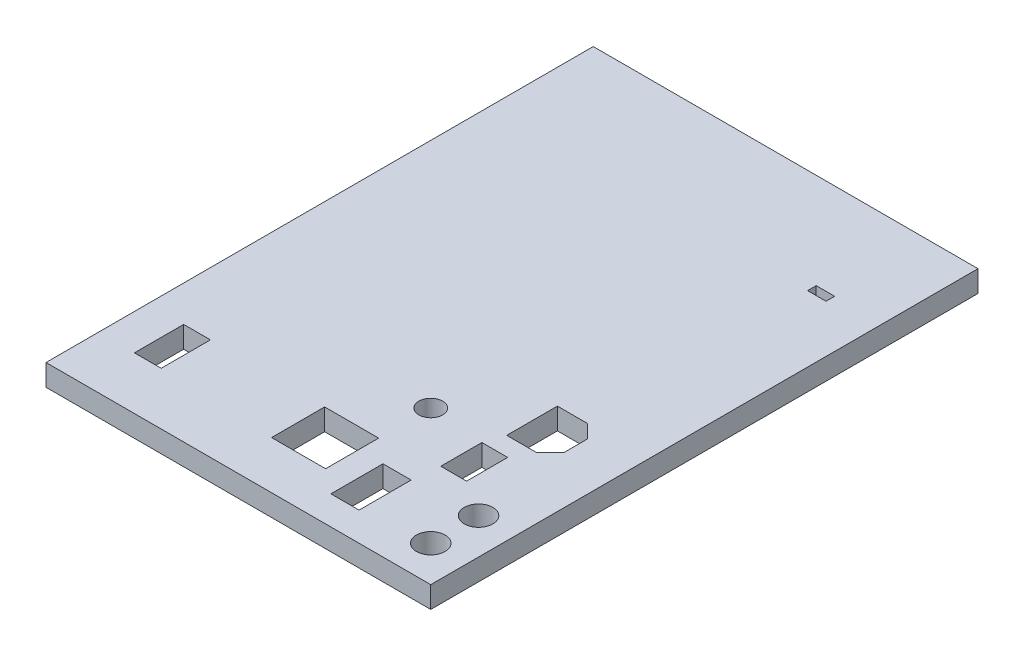
SolidWorks part; units mm, degrees
material "Perspex (TM) GS Acrylic Cast Sheet"
ref_plane "Front Plane" through (0, 0, 0) normal (0, 0, 1) x (1, 0, 0)
ref_plane "Top Plane" through (0, 0, 0) normal (0, 1, 0) x (1, 0, 0)
ref_plane "Right Plane" through (0, 0, 0) normal (1, 0, 0) x (0, 0, -1)
sketch "Sketch1" plane through (0, 0, 0) normal (0, 1, 0) x (1, 0, 0)
  line L1 (-80.5, -114.5) -> (80.5, -114.5)
  line L2 (-80.5, -114.5) -> (-80.5, 114.5)
  line L3 (-80.5, 114.5) -> (80.5, 114.5)
  line L4 (80.5, -114.5) -> (80.5, 114.5)
  line L5 (-80.5, -114.5) -> (80.5, 114.5) construction
  line L6 (-80.5, 114.5) -> (80.5, -114.5) construction
  point P0 (0, 0)
  dimension "D1" = 161
  dimension "D2" = 229
extrude "Boss-Extrude1" add sketch "Sketch1" along normal blind 9
sketch "Sketch2" plane through (0, 9, 0) normal (0, 1, 0) x (1, 0, 0)
  line L0 (65.5, -79.5) -> (65.5, -99.5) construction
  line L1 (80.5, -114.5) -> (80.5, 114.5) construction
  line L2 (38.5, -102.5) -> (26.7, -102.5)
  line L3 (38.5, -102.5) -> (38.5, -80.7)
  line L4 (38.5, -80.7) -> (26.7, -80.7)
  line L5 (26.7, -102.5) -> (26.7, -80.7)
  line L6 (-80.5, -114.5) -> (80.5, -114.5) construction
  line L7 (-80.5, 114.5) -> (-80.5, -114.5) construction
  line L8 (16.5, -94.5) -> (-6.1, -94.5)
  line L9 (16.5, -94.5) -> (16.5, -72.3)
  line L10 (16.5, -72.3) -> (-6.1, -72.3)
  line L11 (-6.1, -94.5) -> (-6.1, -72.3)
  line L12 (-54.3, -92.5) -> (-65.5, -92.5)
  line L13 (-54.3, -92.5) -> (-54.3, -71.9)
  line L14 (-54.3, -71.9) -> (-65.5, -71.9)
  line L15 (-65.5, -92.5) -> (-65.5, -71.9)
  line L16 (80.5, 114.5) -> (-80.5, 114.5) construction
  line L17 (42.3, -23.3) -> (54.9, -23.3)
  line L18 (42.3, -23.3) -> (42.3, -44.5)
  line L19 (42.3, -44.5) -> (54.9, -44.5)
  line L21 (52.8, 74.5) -> (60.5, 74.5)
  line L22 (52.8, 74.5) -> (52.8, 70.9)
  line L23 (52.8, 70.9) -> (60.5, 70.9)
  line L24 (60.5, 74.5) -> (60.5, 70.9)
  line L25 (54.9, -44.5) -> (60.5, -38.9)
  line L26 (60.5, -38.9) -> (60.5, -28.9)
  line L27 (60.5, -28.9) -> (54.9, -23.3)
  line L29 (39.7, -69.5) -> (50.5, -69.5)
  line L30 (39.7, -69.5) -> (39.7, -52.3)
  line L31 (39.7, -52.3) -> (50.5, -52.3)
  line L32 (50.5, -69.5) -> (50.5, -52.3)
  line L33 (39.7, -69.5) -> (50.5, -52.3) construction
  line L34 (39.7, -52.3) -> (50.5, -69.5) construction
  circle A0 centre (16.5, -50.5) radius 5
  circle A1 centre (65.5, -99.5) radius 6
  circle A2 centre (65.5, -79.5) radius 6
  point P36 (50.0185, -58.4743)
  point P38 (45.1, -60.9)
  dimension "D19" = 12
  dimension "D27" = 10
  dimension "D1" = 42
  dimension "D2" = 12
  dimension "D3" = 20
  dimension "D4" = 64
  dimension "D5" = 15
  dimension "D6" = 22
  dimension "D7" = 64
  dimension "D8" = 64
  dimension "D9" = 135
  dimension "D10" = 70
  dimension "D11" = 40
  dimension "D12" = 20
  dimension "D13" = 7.7
  dimension "D14" = 3.6
  dimension "D15" = 20
  dimension "D16" = 18.2
  dimension "D17" = 21.2
  dimension "D18" = 10
  dimension "D20" = 20
  dimension "D21" = 15
  dimension "D22" = 15
  dimension "D23" = 30
  dimension "D24" = 45
  dimension "D25" = 10.8
  dimension "D26" = 17.2
  dimension "D28" = 11.8
  dimension "D29" = 21.8
  dimension "D30" = 22.2
  dimension "D31" = 22.6
  dimension "D32" = 11.2
  dimension "D33" = 20.6
extrude "Cut-Extrude1" cut sketch "Sketch2" against normal through all
equation "\"PCLength\"= 143mm'Length across I/O from PS to GPU"
equation "\"PCWidth\"= 340mm'Distance of longest part parallel to GPU(ussually GPU)"
equation "\"PCHeight\"= 190mm'Tallest point with mobo laying flat"
equation "\"WallThickness\"= 9mm'Thickness of each outer tank wall"
equation "\"ThermoBarrierThickness\"= 6mm'Thickness of barrier between hot side and cold side"
equation "\"HotSideGap\"= 15mm'Space in the hot side that hot fluid flows into"
equation "\"PCClearance\"= 40mm'Clearance from top of tank to top of PC"
equation "\"RadiatorHeight\"= 277.37mm'Final Height from ground of radiators"
equation "\"AirflowGap\"= 26mm'Distance between radiators and tank for airflow"
equation "\"VolumeSubtraction\"= 230mm"
equation "\"D1@Sketch1\"=\"PCLength\" + (2 * \"WallThickness\")"
equation "\"D1@Boss-Extrude1\"=\"WallThickness\""
equation "\"D2@Sketch1\"=\"PCHeight\" + \"ThermoBarrierThickness\" + \"HotSideGap\" + (2 * \"WallThickness\")"
